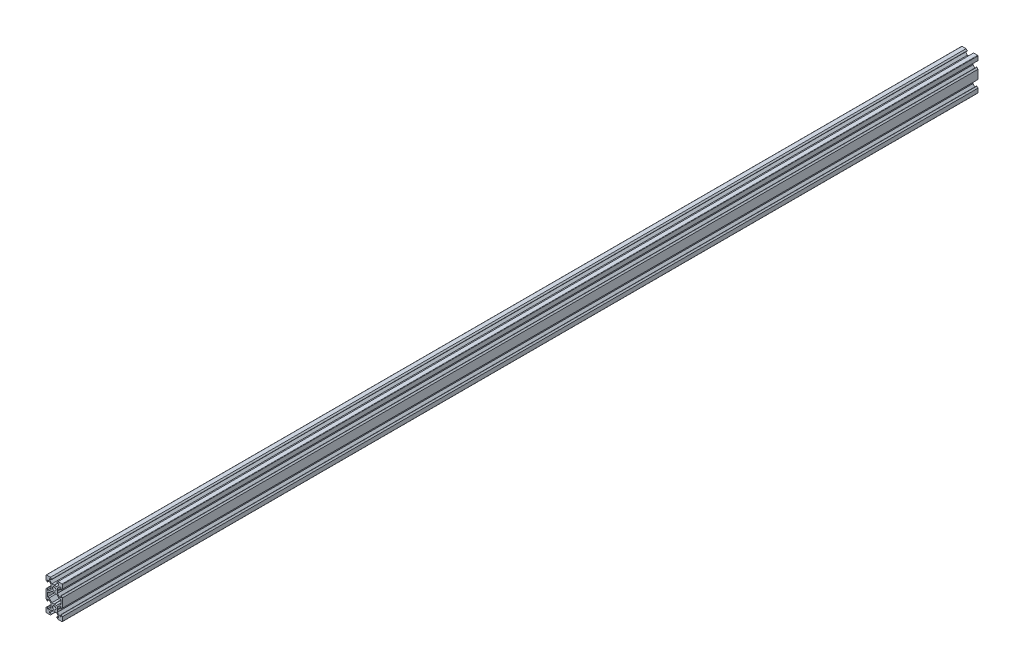
SolidWorks part; units mm, degrees
ref_plane "Plan de face" through (0, 0, 0) normal (0, 0, 1) x (1, 0, 0)
ref_plane "Plan de dessus" through (0, 0, 0) normal (0, 1, 0) x (1, 0, 0)
ref_plane "Plan de droite" through (0, 0, 0) normal (1, 0, 0) x (0, 0, -1)
ref_axis "Axe" through (0, 0, -13.782) along (0, 0, 1)
sketch "Esquisse1" plane through (0, 0, 0) normal (0, 0, 1) x (1, 0, 0)
  line L0 (0, 22.8977) -> (0, -22.8977) construction
  line L1 (-33.6074, 0) -> (33.6074, 0) construction
  line L2 (0, 0) -> (-22.2114, 22.2114) construction
  line L3 (-9.5, 10) -> (-4.58, 10)
  line L4 (-4.58, 10) -> (-3.125, 8.545)
  line L5 (-3.125, 8.545) -> (-3.125, 8.2)
  line L6 (-3.125, 8.2) -> (-5.5, 8.2)
  line L7 (-2.8393, 3.9) -> (-5.5, 6.5607)
  line L8 (-2.8393, 3.9) -> (-0.21, 3.9)
  line L9 (-5.5, 6.5607) -> (-5.5, 8.2)
  line L10 (0, 3.69) -> (0, 2.1)
  line L11 (-3.9, 2.8393) -> (-6.5607, 5.5)
  line L12 (-8.545, 3.125) -> (-8.2, 3.125)
  line L13 (-8.2, 3.125) -> (-8.2, 5.5)
  line L14 (-6.5607, 5.5) -> (-8.2, 5.5)
  line L15 (-10, 4.58) -> (-8.545, 3.125)
  line L16 (-10, 9.5) -> (-10, 4.58)
  line L17 (-0.21, 3.9) -> (0, 3.69)
  line L18 (-3.9, 2.8393) -> (-3.9, 0.21)
  line L20 (-3.9, 0.21) -> (-3.69, 0)
  line L21 (-0.21, -3.9) -> (0, -3.69)
  line L22 (0, -3.69) -> (0, -2.1)
  line L23 (-6.5607, -5.5) -> (-8.2, -5.5)
  line L24 (-2.8393, -3.9) -> (-0.21, -3.9)
  line L25 (-8.545, -3.125) -> (-8.2, -3.125)
  line L26 (-10, -4.58) -> (-8.545, -3.125)
  line L27 (-8.2, -3.125) -> (-8.2, -5.5)
  line L28 (-2.8393, -3.9) -> (-6.2393, -7.3)
  line L29 (-3.9, -2.8393) -> (-6.5607, -5.5)
  line L30 (-3.9, -2.8393) -> (-3.9, -0.21)
  line L31 (-3.9, -0.21) -> (-3.69, 0)
  line L32 (-6.2393, -7.3) -> (-8.2, -7.3)
  line L33 (-8.2, -7.3) -> (-8.2, -10)
  line L34 (-8.2, -10) -> (-10, -10)
  line L35 (-10, -10) -> (-10, -4.58)
  arc A0 (0, -2.1) -> (0, 2.1) centre (0, 0) cw
  arc A1 (-9.5, 10) -> (-10, 9.5) centre (-9.5, 9.5) ccw
  point P4 (0, 0)
  point P7 (0, 0)
  point P30 (-10, 10)
  dimension "D5" = 11
  dimension "D2" = 2.1
  dimension "D3" = 6.25
  dimension "D10" = 0.5
  dimension "D4" = 9.16
  dimension "D6" = 1.5
  dimension "D7" = 1.8
  dimension "D8" = 4.3
  dimension "D9" = 20
  dimension "D11" = 0.42
  dimension "D12" = 10
  dimension "D13" = 1.8
extrude "Boss.-Extru.1" add sketch "Esquisse1" along normal blind 1120
sketch "Esquisse3" plane through (0, 0, 1120) normal (0, 0, 1) x (1, 0, 0)
  line L0 (0, 0) -> (-9.8536, 9.8536) construction
  line L1 (-8.2, 8.2) -> (-8.2, 6.57)
  line L2 (-8.2, 6.57) -> (-7.54, 6.57)
  line L3 (-7.54, 6.57) -> (-6.57, 7.54)
  line L4 (-8.2, 3.125) -> (-8.2, 5.5) construction
  line L5 (-6.57, 8.2) -> (-6.57, 7.54)
  line L6 (-8.2, 8.2) -> (-6.57, 8.2)
  line L7 (-5.5, 6.5607) -> (-5.5, 8.2) construction
  arc A0 (-9.5, 10) -> (-10, 9.5) centre (-9.5, 9.5) ccw construction
  point P13 (-7.055, 7.055)
  point P14 (-6.57, 7.87)
  dimension "D1" = 1.07
extrude "Enlèv. mat.-Extru.1" [suppressed] cut sketch "Esquisse3" against normal through all
mirror "Symétrie1" about plane through (0, 3.69, 1120) normal (-1, 0, 0) of "Enlèv. mat.-Extru.1", "Boss.-Extru.1"
mirror "Symétrie6" about plane through (-8.2, -10, 1120) normal (0, 1, 0) of "Symétrie1", "Boss.-Extru.1"
